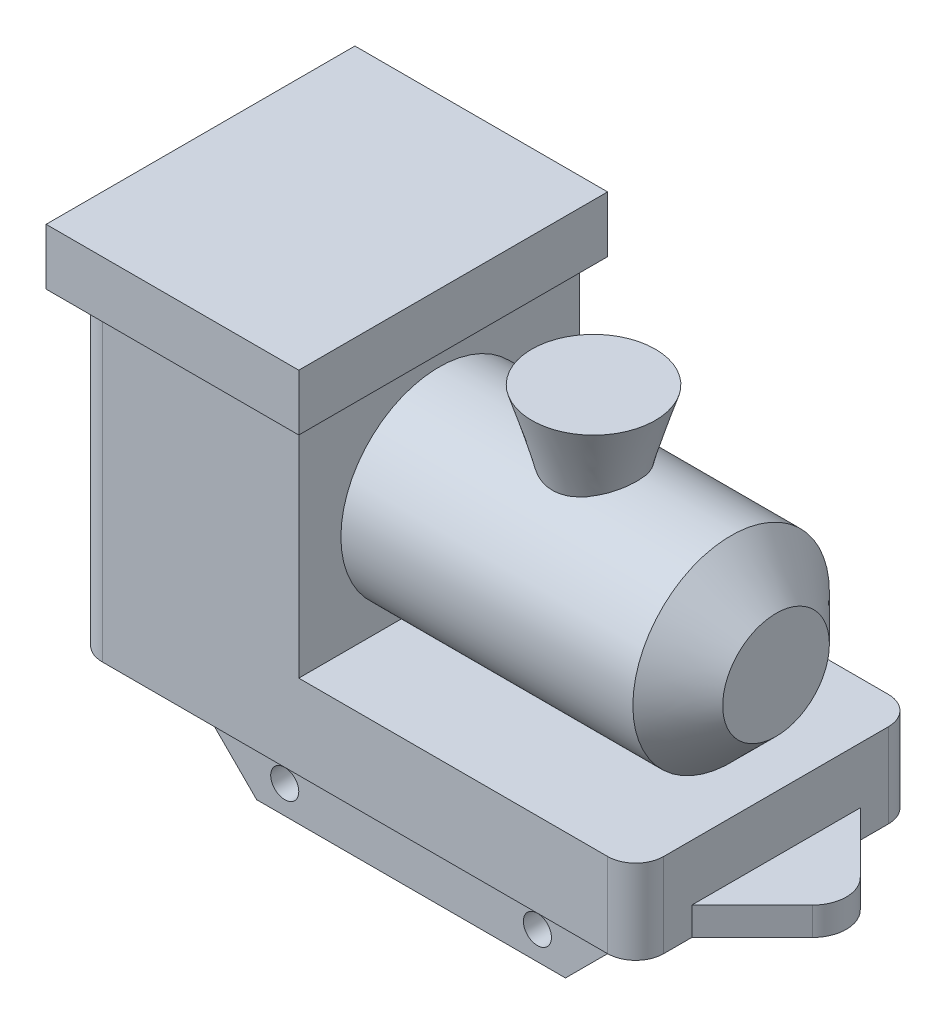
SolidWorks part; units mm, degrees
material "Cast Alloy Steel"
ref_plane "Front Plane" through (0, 0, 0) normal (0, 0, 1) x (1, 0, 0)
ref_plane "Top Plane" through (0, 0, 0) normal (0, 1, 0) x (1, 0, 0)
ref_plane "Right Plane" through (0, 0, 0) normal (1, 0, 0) x (0, 0, -1)
sketch "Sketch1" plane through (0, 0, 0) normal (0, 1, 0) x (1, 0, 0)
  line L1 (-50, -25) -> (50, -25)
  line L2 (-50, -25) -> (-50, 25)
  line L3 (-50, 25) -> (50, 25)
  line L4 (50, -25) -> (50, 25)
  line L5 (-50, -25) -> (50, 25) construction
  line L6 (-50, 25) -> (50, -25) construction
  point P0 (0, 0)
  dimension "D1" = 100
  dimension "D2" = 50
extrude "Boss-Extrude1" add sketch "Sketch1" along normal blind 15
shell "Shell1" thickness 5 removed face at (0, 15, 0)
fillet "Fillet1" radius 5 4 edges at (-50, 7.5, -25) (50, 7.5, -25) (50, 7.5, 25) (-50, 7.5, 25)
sketch "Sketch2" plane through (0, 0, 0) normal (0, 0, 1) x (1, 0, 0)
  line L0 (-45, 0) -> (-27.5, -17.5)
  line L1 (-45, 0) -> (45, 0) construction
  line L2 (-27.5, -17.5) -> (27.5, -17.5)
  line L3 (27.5, -17.5) -> (45, 0)
  line L4 (-50, 0) -> (-50, 15) construction
  line L5 (50, 15) -> (50, 0) construction
  line L6 (-22.5, -12.5) -> (22.5, -12.5) construction
  line L7 (45, 0) -> (-45, 0)
  circle A0 centre (-22.5, -12.5) radius 2.5
  circle A1 centre (22.5, -12.5) radius 2.5
  point P10 (0, -17.5)
  point P16 (0, -12.5)
  dimension "D5" = 5
  dimension "D6" = 45
  dimension "D1" = 5
  dimension "D2" = 17.5
  dimension "D3" = 5
  dimension "D4" = 45
  dimension "D7" = 5
extrude "Boss-Extrude2" add sketch "Sketch2" along normal mid plane 30
sketch "Sketch3" plane through (0, 0, 0) normal (0, 1, 0) x (1, 0, 0)
  line L6 (50, 15) -> (60.7574, 4.2426)
  line L10 (50, -20) -> (50, 20) construction
  line L11 (60.7574, -4.2426) -> (50, -15)
  line L12 (50, 15) -> (50, -15)
  arc A4 (60.7574, 4.2426) -> (60.7574, -4.2426) centre (56.5147, 0) cw
  dimension "D7" = 6
  dimension "D6" = 30
  dimension "D8" = 45
  dimension "D9" = 45
extrude "Boss-Extrude3" add sketch "Sketch3" along normal blind 5
sketch "Sketch4" plane through (0, 0, 0) normal (0, 1, 0) x (1, 0, 0)
  line L0 (-50, 15) -> (-60.7574, 4.2426)
  line L5 (-50, 20) -> (-50, -20) construction
  line L6 (-60.7574, -4.2426) -> (-50, -15)
  line L7 (-50, 15) -> (-50, -15)
  arc A1 (-60.7574, 4.2426) -> (-60.7574, -4.2426) centre (-56.5147, 0) ccw
  circle A6 centre (-56.5147, 0) radius 3.5
  dimension "D4" = 6
  dimension "D5" = 7
  dimension "D1" = 30
  dimension "D2" = 45
  dimension "D3" = 45
ref_plane "Plane1" through (0, 5, 0) normal (0, -1, 0) x (-1, 0, 0)
extrude "Boss-Extrude4" add sketch "Sketch4" along normal blind 5 from surface starting at plane "Plane1"
sketch "Sketch5" plane through (0, 5, 0) normal (0, 1, 0) x (1, 0, 0)
  line L0 (-45, 20) -> (45, 20)
  line L1 (45, 20) -> (-45, 20) construction
  line L2 (45, 20) -> (45, -20)
  line L3 (45, -20) -> (-45, -20)
  line L4 (-45, -20) -> (-45, 20)
extrude "Boss-Extrude5" add sketch "Sketch5" along normal blind 10
sketch "Sketch6" plane through (0, 15, 0) normal (0, 1, 0) x (1, 0, 0)
  line L0 (45, -25) -> (-45, -25)
  line L3 (-45, -25) -> (-10, -25)
  line L5 (-10, 25) -> (-45, 25)
  line L6 (-50, 20) -> (-50, -20)
  line L7 (-10, -25) -> (-10, 25)
  arc A0 (-45, 25) -> (-50, 20) centre (-45, 20) ccw
  arc A3 (-45, -25) -> (-50, -20) centre (-45, -20) cw
  line M7 (45, 25) -> (-45, 25)
  arc M8 (-45, 25) -> (-50, 20) centre (-45, 20) ccw
  line M9 (-50, 20) -> (-50, -20)
  arc M10 (-50, -20) -> (-45, -25) centre (-45, -20) ccw
  line M11 (-45, -25) -> (45, -25)
  dimension "D4" = 5
  dimension "D1" = 40
  dimension "D5" = 35
extrude "Boss-Extrude6" add sketch "Sketch6" along normal blind 40 contours L7 M11 M7 M8 M9 M10 region at (-29.8981, 15, 0)
sketch "Sketch7" plane through (0, 55, 0) normal (0, 1, 0) x (1, 0, 0)
  line L0 (-52.5, -27.5) -> (-7.5, -27.5)
  line L3 (-7.5, -27.5) -> (-7.5, 27.5)
  line L4 (-7.5, 27.5) -> (-52.5, 27.5)
  line L5 (-52.5, 27.5) -> (-52.5, -27.5)
  line L6 (-10, 25) -> (-45, 25) construction
  line L8 (-10, -25) -> (-10, 25) construction
  dimension "D1" = 45
  dimension "D2" = 55
  dimension "D3" = 2.5
  dimension "D4" = 2.5
extrude "Boss-Extrude7" add sketch "Sketch7" along normal blind 10
sketch "Sketch8" plane through (-10, 0, 0) normal (1, 0, 0) x (0, 0, -1)
  line L1 (-27.5, 55) -> (27.5, 55) construction
  circle A2 centre (0, 33) radius 17.5
  point P5 (0, 55)
  dimension "D1" = 35
  dimension "D2" = 33
extrude "Boss-Extrude8" add sketch "Sketch8" along normal blind 60
chamfer "Chamfer1" distance 8 angle 45 1 edges at (50, 33, -17.5)
ref_plane "Plane2" through (0, 47.5, 0) normal (0, 1, 0) x (1, 0, 0)
sketch "Sketch10" plane through (0, 47.5, 0) normal (0, 1, 0) x (1, 0, 0)
  line L0 (-7.5, -27.5) -> (-7.5, 27.5) construction
  line L1 (45, 25) -> (-10, 25) construction
  circle A0 centre (17.5, 0) radius 7
  dimension "D1" = 14
  dimension "D2" = 25
  dimension "D3" = 25
ref_plane "Plane3" through (0, 61.5, 0) normal (0, 1, 0) x (1, 0, 0)
sketch "Sketch9" plane through (0, 61.5, 0) normal (0, 1, 0) x (1, 0, 0)
  line L0 (-7.5, -27.5) -> (-7.5, 27.5) construction
  line L1 (45, 25) -> (-10, 25) construction
  circle A0 centre (17.5, 0) radius 11
  dimension "D2" = 22
  dimension "D3" = 25
  dimension "D1" = 25
loft "Loft1" add profiles "Sketch9", "Sketch10" connector at (20.8466, 61.5, 10.4786) connector at (21.9755, 47.5, 5.3824)
